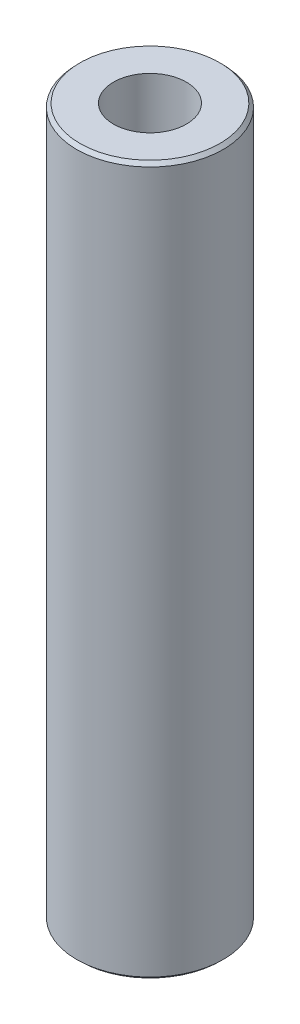
SolidWorks part; units mm, degrees
ref_plane "Front Plane" through (0, 0, 0) normal (0, 0, 1) x (1, 0, 0)
ref_plane "Top Plane" through (0, 0, 0) normal (0, 1, 0) x (1, 0, 0)
ref_plane "Right Plane" through (0, 0, 0) normal (1, 0, 0) x (0, 0, -1)
sketch "Sketch1" plane through (0, 0, 0) normal (0, 1, 0) x (1, 0, 0)
  circle A0 centre (0, 0) radius 60
  dimension "SHAFT_OD" = 120
extrude "Boss-Extrude1" add sketch "Sketch1" along normal blind 580.0261
sketch "Sketch2" plane through (0, 0, 0) normal (0, 1, 0) x (1, 0, 0)
  circle A0 centre (0, 0) radius 29.8431
  dimension "BORE_D" = 59.6861
extrude "Cut-Extrude1" cut sketch "Sketch2" along normal through all
chamfer "Chamfer1" distance 2.906 angle 43.064 2 edges at (0, 580.0261, 60) (0, 0, 60) first distance on face at (0, 580.0261, 60) first distance on face at (0, 0, 29.8431)
